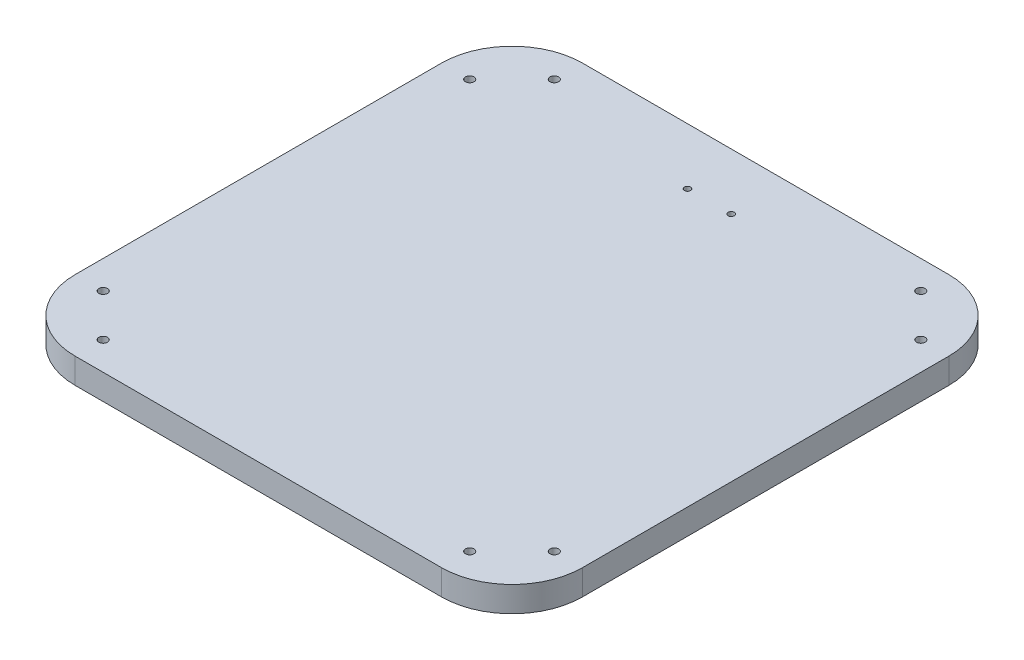
SolidWorks part; units mm, degrees
ref_plane "Front Plane" through (0, 0, 0) normal (0, 0, 1) x (1, 0, 0)
ref_plane "Top Plane" through (0, 0, 0) normal (0, 1, 0) x (1, 0, 0)
ref_plane "Right Plane" through (0, 0, 0) normal (1, 0, 0) x (0, 0, -1)
sketch "Sketch1" plane through (0, 0, 0) normal (0, 1, 0) x (1, 0, 0)
  line L1 (-65, -90) -> (65, -90)
  line L2 (-90, -65) -> (-90, 65)
  line L3 (-65, 90) -> (65, 90)
  line L4 (90, -65) -> (90, 65)
  arc A0 (-90, 65) -> (-65, 90) centre (-65, 65) cw
  arc A1 (65, 90) -> (90, 65) centre (65, 65) cw
  arc A2 (90, -65) -> (65, -90) centre (65, -65) cw
  arc A3 (-65, -90) -> (-90, -65) centre (-65, -65) cw
  point P4 (-90, 0)
  point P6 (0, 90)
  dimension "D3" = 25
  dimension "D1" = 180
  dimension "D2" = 180
extrude "Plate" add sketch "Sketch1" along normal blind 9
sketch "Sketch2" plane through (0, 9, 0) normal (0, 1, 0) x (1, 0, 0)
  line L0 (-7.747, 70) -> (7.747, 70) construction
  line L1 (0, 90) -> (0, 70) construction
  line L2 (-65, 90) -> (65, 90) construction
  circle A1 centre (-7.747, 70) radius 1.09
  circle A2 centre (7.747, 70) radius 1.09
  dimension "D3" = 2.18
  dimension "D1" = 15.494
  dimension "D2" = 20
extrude "Caster Holes" cut sketch "Sketch2" against normal through all
sketch "Sketch3" plane through (0, 9, 0) normal (0, 1, 0) x (1, 0, 0)
  line L0 (-65, 90) -> (-65, -90) construction
  line L1 (65, 90) -> (65, -90) construction
  line L2 (-90, 65) -> (90, 65) construction
  line L3 (-90, -65) -> (90, -65) construction
  circle A0 centre (-65, 80) radius 1.525
  circle A1 centre (-80, 65) radius 1.525
  circle A2 centre (80, 65) radius 1.525
  circle A3 centre (80, -65) radius 1.525
  circle A4 centre (65, 80) radius 1.525
  circle A5 centre (65, -80) radius 1.525
  circle A6 centre (-65, -80) radius 1.525
  circle A7 centre (-80, -65) radius 1.525
  dimension "D1" = 3.05
  dimension "D2" = 15
  dimension "D3" = 15
  dimension "D4" = 15
  dimension "D5" = 15
  dimension "D6" = 15
  dimension "D7" = 15
  dimension "D8" = 15
  dimension "D9" = 15
extrude "Hex Holes" cut sketch "Sketch3" against normal through all
